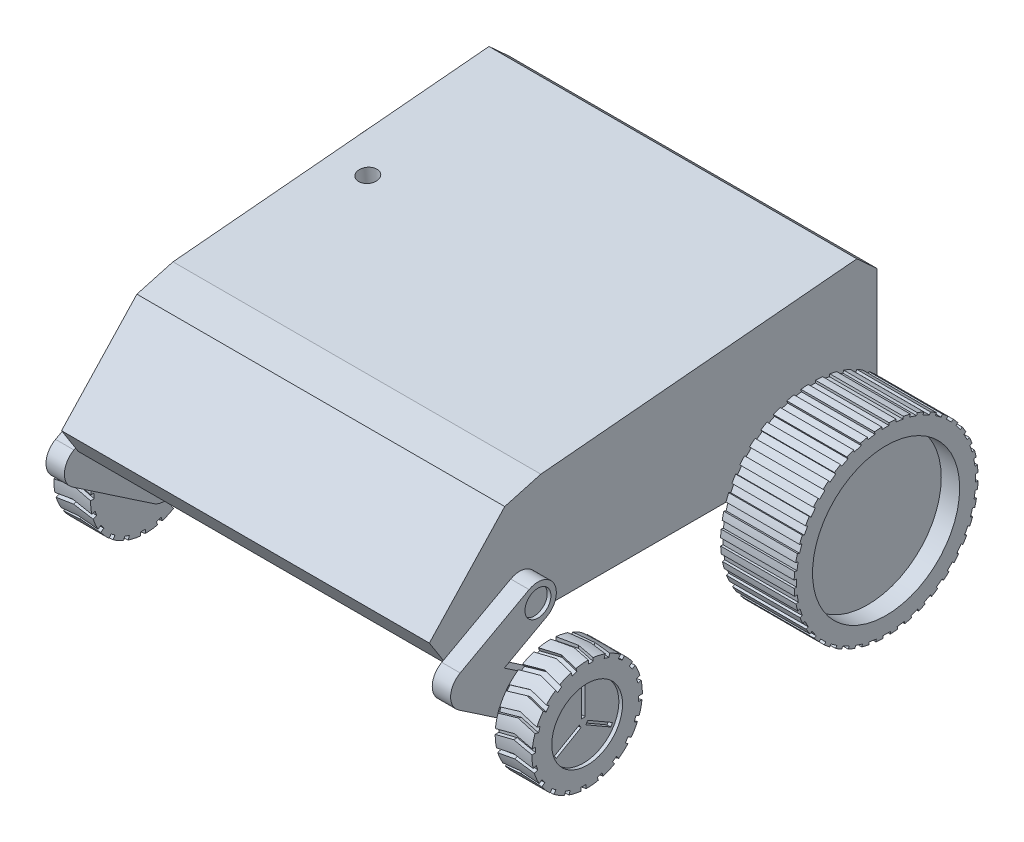
SolidWorks part; units mm, degrees
ref_plane "Front Plane" through (0, 0, 0) normal (0, 0, 1) x (1, 0, 0)
ref_plane "Top Plane" through (0, 0, 0) normal (0, 1, 0) x (1, 0, 0)
ref_plane "Right Plane" through (0, 0, 0) normal (1, 0, 0) x (0, 0, -1)
sketch "Sketch2" plane through (0, 0, 0) normal (1, 0, 0) x (0, 0, -1)
  line L0 (-52.0687, 63.5218) -> (-71.6998, 58.0966)
  line L1 (-52.0687, 63.5218) -> (119.7486, 79.0171)
  line L2 (130.6468, 69.0576) -> (130.6468, 10)
  line L3 (120.6468, 0) -> (-103.5956, 0)
  line L4 (119.7486, 79.0171) -> (130.6468, 69.0576)
  line L5 (130.6468, 10) -> (120.6468, 0)
  line L6 (-103.5956, 0) -> (-112.6731, 14.3039)
  line L7 (-71.6998, 58.0966) -> (-112.6731, 14.3039)
  point P9 (-119.3532, 0)
  point P12 (130.6468, 0)
  point P15 (130.6468, 80)
  dimension "D1" = 250
  dimension "D2" = 80
extrude "Boss-Extrude1" add sketch "Sketch2" along normal mid plane 200
sketch "Sketch3" plane through (100, 0, 0) normal (1, 0, 0) x (0, 0, -1)
  line L0 (-51.2866, -28.5858) -> (-81.9473, -7.8301)
  line L1 (-62.4982, -45.1478) -> (-106.7272, -15.2071)
  line L2 (-68.4475, 22.3607) -> (-105.9232, 1.8456)
  line L3 (-58.8438, 4.8173) -> (-81.9473, -7.8301)
  circle A0 centre (-63.6457, 13.589) radius 10
  arc A1 (-105.9232, 1.8456) -> (-106.7272, -15.2071) centre (-101.1213, -6.9261) ccw
  circle A2 centre (-56.8924, -36.8668) radius 10
  line M4 (-112.6731, 14.3039) -> (-103.5956, 0)
  line M5 (-103.5956, 0) -> (120.6468, 0)
  dimension "D1" = 20
extrude "Boss-Extrude2" add sketch "Sketch3" along normal blind 10 contours A0 L2 L3 M4 M5 | A0 | A2 L0 L3 L2 A1 L1 M5 M4 | A2 region at (100, -16.5858, 84.801) region at (100, -36.8668, 56.8924) region at (100, 6.3637, 82.8379) region at (100, 13.589, 63.6457)
sketch "Sketch4" plane through (110, 0, 0) normal (1, 0, 0) x (0, 0, -1)
  circle A0 centre (-63.6457, 13.589) radius 7.0604
extrude "Cut-Extrude1" cut sketch "Sketch4" against normal blind 2
sketch "Sketch5" plane through (110, 0, 0) normal (1, 0, 0) x (0, 0, -1)
  circle A0 centre (-56.8924, -36.8668) radius 30
  dimension "D1" = 60
extrude "Boss-Extrude3" add sketch "Sketch5" along normal blind 20
sketch "Sketch6" plane through (130, 0, 0) normal (1, 0, 0) x (0, 0, -1)
  circle A0 centre (-56.8924, -36.8668) radius 19.2517
extrude "Cut-Extrude2" cut sketch "Sketch6" against normal blind 2
sketch "Sketch7" plane through (128, 0, 0) normal (1, 0, 0) x (0, 0, -1)
  line L0 (-56.8924, -17.6151) -> (-56.8924, -36.8668) construction
  line L2 (-57.8466, -19.2033) -> (-55.9382, -19.2033)
  line L3 (-57.8466, -19.2033) -> (-57.8466, -34.769)
  line L4 (-57.8466, -34.769) -> (-55.9382, -34.769)
  line L5 (-55.9382, -19.2033) -> (-55.9382, -34.769)
  circle A0 centre (-56.8924, -36.8668) radius 19.2517 construction
extrude "Cut-Extrude3" cut sketch "Sketch7" against normal blind 2
pattern_circular "CirPattern1" count 3 over 360 about axis through (128, -36.8668, 56.8924) along (1, 0, 0) of "Cut-Extrude3"
ref_plane "Plane1" through (0, 0, 26.8924) normal (0, 0, -1) x (-1, 0, 0)
sketch "Sketch8" plane through (0, 0, 26.8924) normal (0, 0, -1) x (-1, 0, 0)
  line L0 (-119.962, -39.5699) -> (-109.0694, -36.9001)
  line L1 (-109.0694, -36.9001) -> (-109.0694, -39.5699)
  line L2 (-109.0694, -39.5699) -> (-119.962, -42.2397)
  line L3 (-119.962, -42.2397) -> (-132.7769, -39.5699)
  line L4 (-132.7769, -39.5699) -> (-132.7769, -36.9001)
  line L5 (-132.7769, -36.9001) -> (-119.962, -39.5699)
extrude "Cut-Extrude4" cut sketch "Sketch8" against normal blind 2
pattern_circular "CirPattern2" count 20 over 360 about axis through (130, -36.8668, 56.8924) along (1, 0, 0) of "Cut-Extrude4"
sketch "Sketch9" plane through (100, 0, 0) normal (1, 0, 0) x (0, 0, -1)
  line L0 (-24.274, -66.8668) -> (50.7754, -66.8668) construction
  line L1 (130.6468, 10) -> (130.6468, 69.0576) construction
  circle A0 centre (95.6468, -16.8668) radius 50
  arc A1 (-48.2057, -65.5816) -> (-42.0195, -62.9206) centre (-56.8924, -36.8668) ccw construction
  dimension "D1" = 100
  dimension "D2" = 35
extrude "Boss-Extrude4" add sketch "Sketch9" along normal blind 40
sketch "Sketch10" plane through (140, 0, 0) normal (1, 0, 0) x (0, 0, -1)
  circle A0 centre (95.6468, -16.8668) radius 40
  dimension "D1" = 80
extrude "Cut-Extrude6" cut sketch "Sketch10" against normal blind 10
sketch "Sketch11" plane through (140, 0, 0) normal (1, 0, 0) x (0, 0, -1)
  line L1 (146.3003, -14.5311) -> (144.3355, -14.5311)
  line L2 (146.3003, -14.5311) -> (146.3003, -18.4608)
  line L3 (146.3003, -18.4608) -> (144.3355, -18.4608)
  line L4 (144.3355, -14.5311) -> (144.3355, -18.4608)
extrude "Cut-Extrude7" cut sketch "Sketch11" against normal blind 40
pattern_circular "CirPattern3" count 40 over 360 about axis through (140, -16.8668, -95.6468) along (1, 0, 0) of "Cut-Extrude7"
ref_plane "Plane2" through (0, 0, 0) normal (1, 0, 0) x (0, 0, -1)
mirror "Mirror1" about plane through (0, 0, 0) normal (1, 0, 0) of "CirPattern2", "Cut-Extrude2", "CirPattern1", "Boss-Extrude3", "Boss-Extrude2", "Boss-Extrude4", "CirPattern3", "Cut-Extrude6"
sketch "Sketch12" plane through (0, 67.6672, 6.1026) normal (0, 0.996, 0.0898) x (1, 0, 0)
  line L0 (0, 126.362) -> (0, -46.1527) construction
  line L1 (100, 126.362) -> (-100, 126.362) construction
  line L2 (100, -46.1527) -> (-100, -46.1527) construction
  line L3 (-100, 40.1046) -> (100, 40.1046) construction
  line L4 (-100, 126.362) -> (-100, -46.1527) construction
  line L5 (100, 126.362) -> (100, -46.1527) construction
  circle A0 centre (-80, 40.1046) radius 5
  dimension "D1" = 10
  dimension "D2" = 20
extrude "Cut-Extrude8" cut sketch "Sketch12" against normal blind 10
sketch "Sketch13" plane through (0, 0, 0) normal (1, 0, 0) x (0, 0, -1)
  line L0 (8.2101, 83.2226) -> (8.2101, -41.8217) construction
